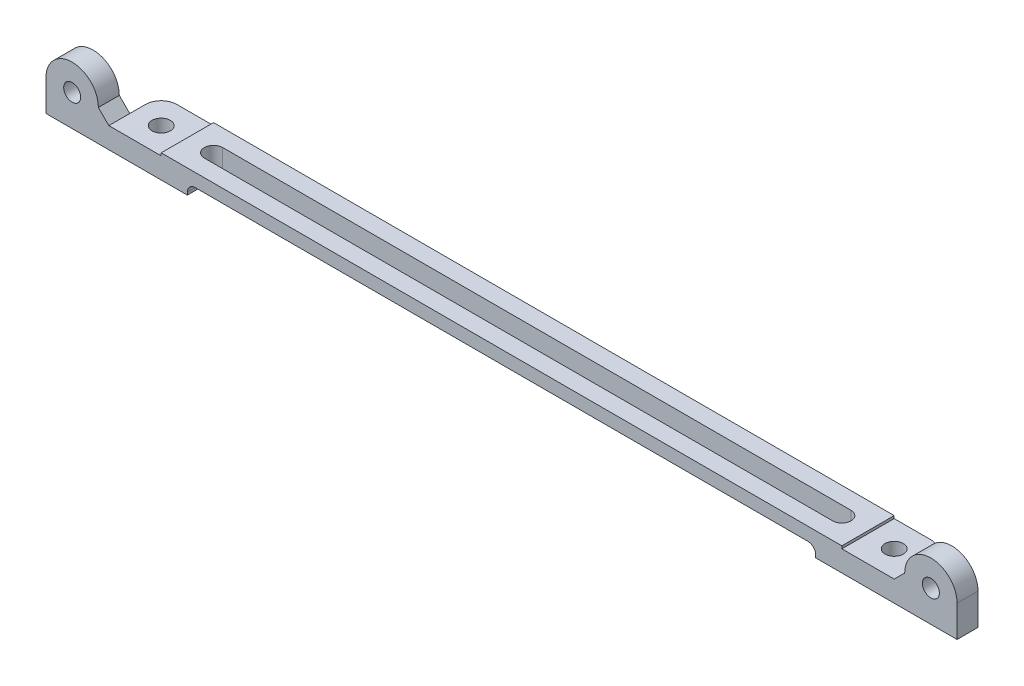
SolidWorks part; units mm, degrees
ref_plane "Front Plane" through (0, 0, 0) normal (0, 0, 1) x (1, 0, 0)
ref_plane "Top Plane" through (0, 0, 0) normal (0, 1, 0) x (1, 0, 0)
ref_plane "Right Plane" through (0, 0, 0) normal (1, 0, 0) x (0, 0, -1)
sketch "Sketch1" plane through (0, 0, 0) normal (0, 1, 0) x (1, 0, 0)
  line L1 (72, 5) -> (-72, 5)
  line L2 (75, 2) -> (75, -5)
  line L3 (75, -5) -> (-75, -5)
  line L4 (-75, 2) -> (-75, -5)
  line L5 (75, 5) -> (-75, -5) construction
  line L6 (75, -5) -> (-75, 5) construction
  line L7 (60, -1.75) -> (-60, -1.75)
  line L8 (60, -1.75) -> (60, 1.75)
  line L9 (60, 1.75) -> (-60, 1.75)
  line L10 (-60, -1.75) -> (-60, 1.75)
  line L11 (60, -1.75) -> (-60, 1.75) construction
  line L12 (60, 1.75) -> (-60, -1.75) construction
  circle A0 centre (-70, 0) radius 1.75
  circle A1 centre (70, 0) radius 1.75
  arc A2 (75, 2) -> (72, 5) centre (72, 2) ccw
  arc A3 (-72, 5) -> (-75, 2) centre (-72, 2) ccw
  circle A4 centre (-60, 0) radius 1.75
  circle A5 centre (60, 0) radius 1.75
  point P0 (0, 0)
  point P16 (0, 0)
  dimension "D3" = 3.5
  dimension "D6" = 3.5
  dimension "D9" = 3
  dimension "D10" = 3
  dimension "D1" = 10
  dimension "D2" = 150
  dimension "D4" = 5
  dimension "D5" = 5
  dimension "D7" = 5
  dimension "D8" = 5
  dimension "D11" = 3.5
  dimension "D12" = 120
extrude "Boss-Extrude1" add sketch "Sketch1" along normal blind 4 contours L1 A3 L4 L3 L2 A2 A5 L7 A4 L9 A0 A1 region at (73.0583, 0, -3.0583)
sketch "Sketch2" plane through (0, 4, 0) normal (0, 1, 0) x (1, 0, 0)
  line L0 (72, 5) -> (-72, 5) construction
  line L1 (-65, 5) -> (65, 5)
  line L2 (-65, 5) -> (-65, -5)
  line L3 (-65, -5) -> (65, -5)
  line L4 (65, 5) -> (65, -5)
  line L5 (75, -5) -> (-75, -5) construction
  line L6 (-75, 2) -> (-75, -5) construction
  line L7 (75, 2) -> (75, -5) construction
  line L12 (72, 5) -> (-72, 5)
  line L13 (-75, 2) -> (-75, -5)
  line L14 (-75, -5) -> (75, -5)
  line L15 (75, -5) -> (75, 2)
  line L16 (72, 5) -> (-72, 5)
  line L17 (-75, 2) -> (-75, -5)
  line L18 (-75, -5) -> (75, -5)
  line L19 (75, -5) -> (75, 2)
  arc A2 (-72, 5) -> (-75, 2) centre (-72, 2) ccw
  arc A3 (75, 2) -> (72, 5) centre (72, 2) ccw
  arc A4 (-72, 5) -> (-75, 2) centre (-72, 2) ccw
  arc A5 (75, 2) -> (72, 5) centre (72, 2) ccw
  arc M11 (60, 1.75) -> (60, -1.75) centre (60, 0) cw
  line M12 (60, -1.75) -> (-60, -1.75)
  arc M13 (-60, -1.75) -> (-60, 1.75) centre (-60, 0) cw
  line M14 (-60, 1.75) -> (60, 1.75)
  line M17 (72, 5) -> (-72, 5)
  line M20 (-75, -5) -> (75, -5)
  dimension "D1" = 10
  dimension "D2" = 10
  dimension "D3" = 0
extrude "Boss-Extrude2" add sketch "Sketch2" along normal blind 0.5 contours L4 L2 M17 M20 M14 M11 M12 M13 region at (0, 4, -3.6962)
sketch "Sketch3" plane through (0, 0, 5) normal (0, 0, 1) x (1, 0, 0)
  line L0 (0, 0) -> (0, 4.5) construction
  line L1 (-65, 4.5) -> (65, 4.5) construction
  line L2 (75, 0) -> (-75, 0) construction
  line L3 (-58.5, 2) -> (58.5, 2)
  line L4 (-60, 0.5) -> (-60, 0)
  line L5 (-60, 0) -> (60, 0)
  line L6 (60, 0.5) -> (60, 0)
  line L7 (-60, 2) -> (60, 0) construction
  line L8 (-60, 0) -> (60, 2) construction
  arc A0 (58.5, 2) -> (60, 0.5) centre (58.5, 0.5) cw
  arc A1 (-58.5, 2) -> (-60, 0.5) centre (-58.5, 0.5) ccw
  point P5 (0, 1)
  dimension "D3" = 1.5
  dimension "D4" = 1.5
  dimension "D1" = 2
  dimension "D2" = 120
extrude "Cut-Extrude1" cut sketch "Sketch3" against normal blind 2
sketch "Sketch4" plane through (0, 0, 5) normal (0, 0, 1) x (1, 0, 0)
  line L0 (-75, 0) -> (-87, 0)
  line L1 (-87, 0) -> (-87, 6)
  line L2 (-75, 4) -> (-77, 6)
  line L3 (0, 0) -> (0, 4.5) construction
  line L4 (-60, 0) -> (60, 0) construction
  line L5 (-65, 4.5) -> (65, 4.5) construction
  line L6 (75, 4) -> (77, 6)
  line L7 (87, 0) -> (87, 6)
  line L8 (75, 0) -> (87, 0)
  arc A0 (-77, 6) -> (-87, 6) centre (-82, 6) ccw
  circle A1 centre (-82, 6) radius 1.6242
  circle A2 centre (82, 6) radius 1.6242
  arc A3 (77, 6) -> (87, 6) centre (82, 6) cw
  line M7 (75, 0) -> (75, 4)
  line M13 (-75, 4) -> (-75, 0)
  dimension "D1" = 12
  dimension "D2" = 6
  dimension "D3" = 5
extrude "Boss-Extrude3" add sketch "Sketch4" against normal blind 4 contours L2 A0 L1 L0 A1 M13 | A3 L6 L8 L7 A2 M7 region at (-81, 0.1628, 5) region at (76.1151, 4.8849, 5)
